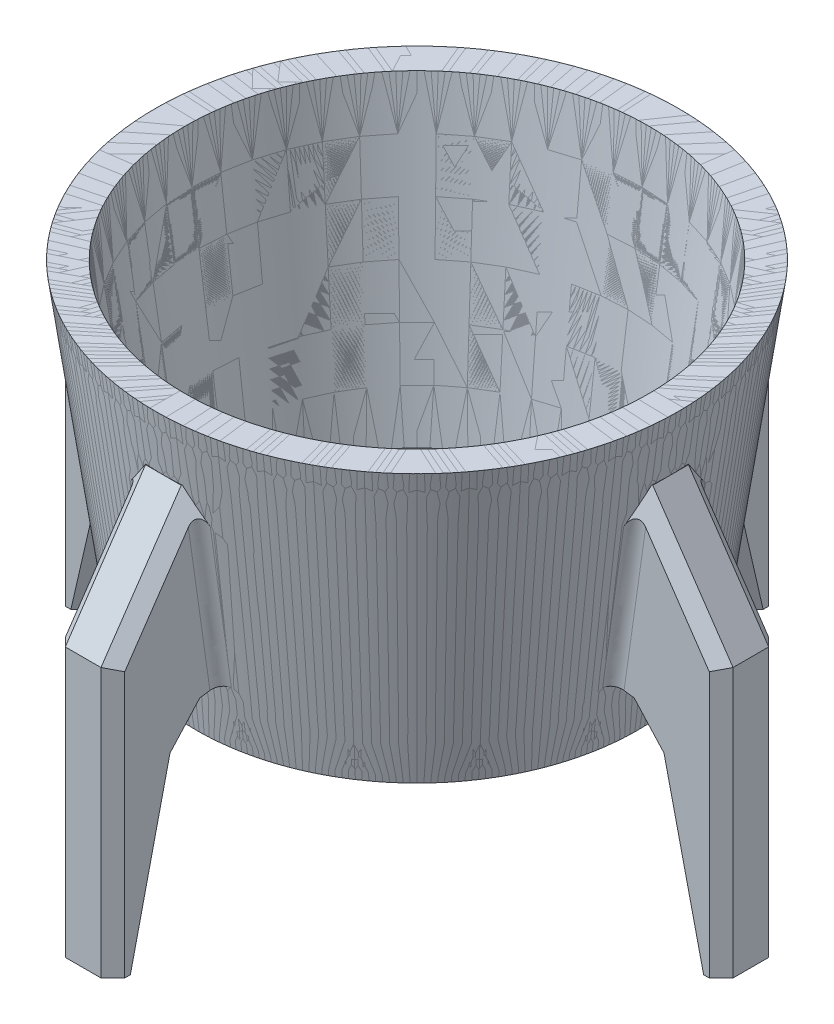
SolidWorks part; units mm, degrees
ref_plane "Front Plane" through (0, 0, 0) normal (0, 0, 1) x (1, 0, 0)
ref_plane "Top Plane" through (0, 0, 0) normal (0, 1, 0) x (1, 0, 0)
ref_plane "Right Plane" through (0, 0, 0) normal (1, 0, 0) x (0, 0, -1)
sketch "Sketch1" plane through (0, 0, 0) normal (0, 0, 1) x (1, 0, 0)
  line L0 (-39, 14.8248) -> (-32, -35.1752)
  line L1 (-32, -35.1752) -> (-37.0488, -35.1752)
  line L2 (-37.0488, -35.1752) -> (-44.0488, 14.8248)
  line L3 (-44.0488, 14.8248) -> (-39, 14.8248)
  line L4 (0, -27.5) -> (0, 27.5) construction
  line L5 (0, 22.278) -> (0, -52.7866) construction
  dimension "D1" = 5
  dimension "D2" = 50
  dimension "D3" = 32
  dimension "D4" = 39
revolve "Revolve1" add sketch "Sketch1" angle 360 about L5
sketch "Sketch4" plane through (0, 0, 0) normal (0, 0, 1) x (1, 0, 0)
  line L0 (-42.6488, 4.8248) -> (-56.1431, -14.9611)
  line L1 (-44.0488, 14.8248) -> (-37.0488, -35.1752) construction
  line L2 (-56.1431, -14.9611) -> (-56.1431, -60.1752)
  line L3 (-56.1431, -60.1752) -> (-51.1431, -60.1752)
  line L4 (-51.1431, -60.1752) -> (-44.7035, -32.1851)
  line L5 (-44.7035, -32.1851) -> (-38.4352, -25.2717)
  line L6 (-38.4352, -25.2717) -> (-42.6488, 4.8248)
  line L7 (-37.0488, -35.1752) -> (37.0488, -35.1752) construction
  dimension "D1" = 5
  dimension "D2" = 10
  dimension "D3" = 10
  dimension "D4" = 25
extrude "Boss-Extrude1" add sketch "Sketch4" along normal blind 5 and the other way blind 5
sketch "Sketch6" plane through (-41.1664, -5.7633, 0) normal (0.9903, 0.1386, 0) x (0, 0, -1)
  line L0 (-5, 10.6914) -> (5, 10.6914)
  line L1 (5, 10.6914) -> (5, -19.6987)
  line L2 (5, -19.6987) -> (-5, -19.6987)
  line L3 (-5, -19.6987) -> (-5, 10.6914)
extrude "Boss-Extrude2" add sketch "Sketch6" along normal up to next (5 mm away)
chamfer "Chamfer1" distance 2 angle 45 8 edges at (-47.9233, -46.1802, -5) (-41.5694, -28.7284, -5) (-47.9233, -46.1802, 5) (-41.5694, -28.7284, 5) (-56.1431, -37.5681, 5) (-49.3959, -5.0681, 5) (-56.1431, -37.5681, -5) (-49.3959, -5.0681, -5)
fillet "Fillet3" radius 2 2 edges
pattern_circular "CirPattern4" count 4 over 360 about axis through (0, 14.8248, 0) along (0, 1, 0) of "Boss-Extrude2"
